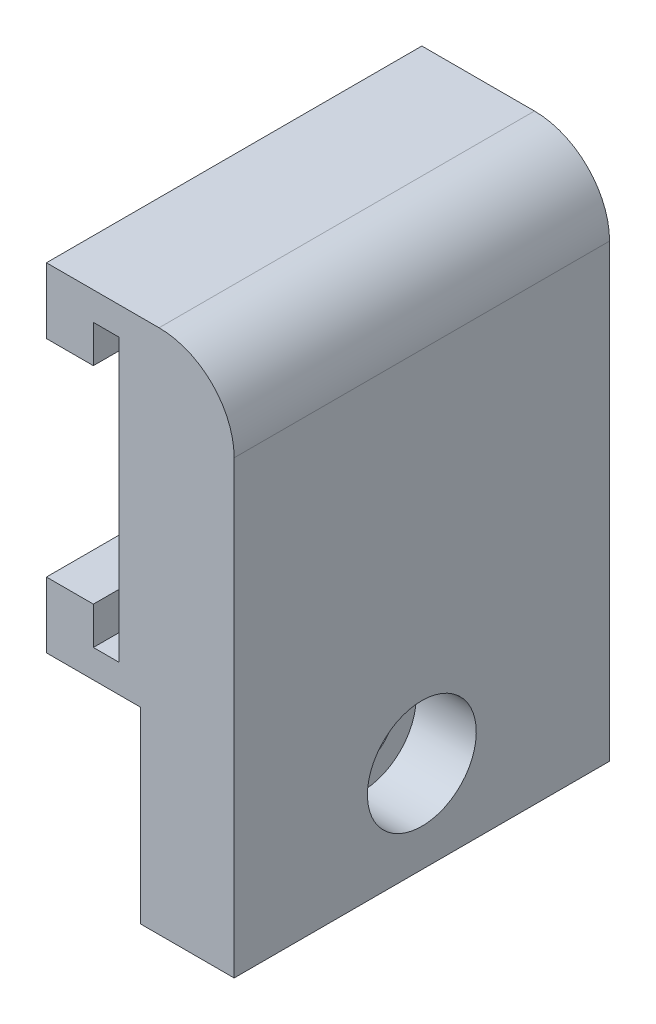
SolidWorks part; units mm, degrees
ref_plane "Front Plane" through (0, 0, 0) normal (0, 0, 1) x (1, 0, 0)
ref_plane "Top Plane" through (0, 0, 0) normal (0, 1, 0) x (1, 0, 0)
ref_plane "Right Plane" through (0, 0, 0) normal (1, 0, 0) x (0, 0, -1)
sketch "Profile" plane through (0, 0, 0) normal (0, 0, 1) x (1, 0, 0)
  line L1 (-6.35, 22.86) -> (6.35, 22.86)
  line L2 (-6.35, 22.86) -> (-6.35, 0)
  line L3 (-6.35, 0) -> (6.35, 0)
  line L4 (6.35, 22.86) -> (6.35, 0)
  line L5 (0, 0) -> (6.35, 0)
  line L6 (0, 0) -> (0, -12.7)
  line L7 (0, -12.7) -> (6.35, -12.7)
  line L8 (6.35, 0) -> (6.35, -12.7)
  dimension "D1" = 22.86
  dimension "D2" = 12.7
  dimension "D3" = 6.35
  dimension "D4" = 12.7
extrude "Boss-Extrude1" add sketch "Profile" along normal mid plane 25.4 contours L4 L1 L2 L3 | L8 L3 L6 L7 region at (0, 11.43, 0) region at (3.175, -6.35, 0)
sketch "ScrewHole" plane through (0, 0, 0) normal (-1, 0, 0) x (0, 0, 1)
  line L2 (12.7, 0) -> (-12.7, 0) construction
  circle A0 centre (0, -6.477) radius 2.159
  point P2 (0, -6.35)
  point P6 (0, -6.35)
  point P7 (0, 0)
  point P11 (-1.0457, -7.8006)
  point P12 (0, 0)
  point P13 (0, -5.9945)
  dimension "D1" = 4.318
  dimension "D2" = 6.477
extrude "Cut-Extrude1" cut sketch "ScrewHole" against normal through all both
sketch "Sketch3" plane through (6.35, 0, 0) normal (1, 0, 0) x (0, 0, -1)
  circle A0 centre (0, -6.477) radius 2.159 construction
  circle A1 centre (0, -6.477) radius 2.159
  circle A2 centre (0, -6.477) radius 3.683
  point P3 (0, 0)
  point P5 (0, 0)
  dimension "D1" = 7.366
extrude "Cut-Extrude2" cut sketch "Sketch3" against normal blind 4.064
sketch "Sketch6" plane through (0, 0, -12.7) normal (0, 0, -1) x (-1, 0, 0)
  line L0 (6.35, 22.86) -> (6.35, 0) construction
  line L1 (1.4478, 20.955) -> (3.175, 20.955)
  line L2 (1.4478, 20.955) -> (1.4478, 1.905)
  line L3 (1.4478, 1.905) -> (3.175, 1.905)
  line L4 (3.175, 20.955) -> (3.175, 18.415)
  line L5 (3.175, 18.415) -> (6.35, 18.415)
  line L6 (3.175, 18.415) -> (3.175, 4.445) construction
  line L7 (3.175, 4.445) -> (6.35, 4.445)
  line L8 (6.35, 18.415) -> (6.35, 4.445) construction
  line L9 (3.175, 18.415) -> (3.175, 4.445) construction
  line L10 (3.175, 4.445) -> (3.175, 1.905)
  line L12 (6.35, 18.415) -> (7.62, 18.415)
  line L13 (6.35, 18.415) -> (6.35, 4.445) construction
  line L14 (6.35, 4.445) -> (7.62, 4.445)
  line L15 (7.62, 18.415) -> (7.62, 4.445)
  point P8 (1.4478, 11.43)
  point P12 (6.35, 11.43)
  point P18 (6.35, 11.43)
  dimension "D1" = 1.7272
  dimension "D2" = 19.05
  dimension "D3" = 13.97
  dimension "D4" = 3.175
  dimension "D5" = 1.27
extrude "Cut-Extrude3" cut sketch "Sketch6" against normal through all both
fillet "Fillet3" radius 5.08 1 edges at (6.35, 22.86, 0)
